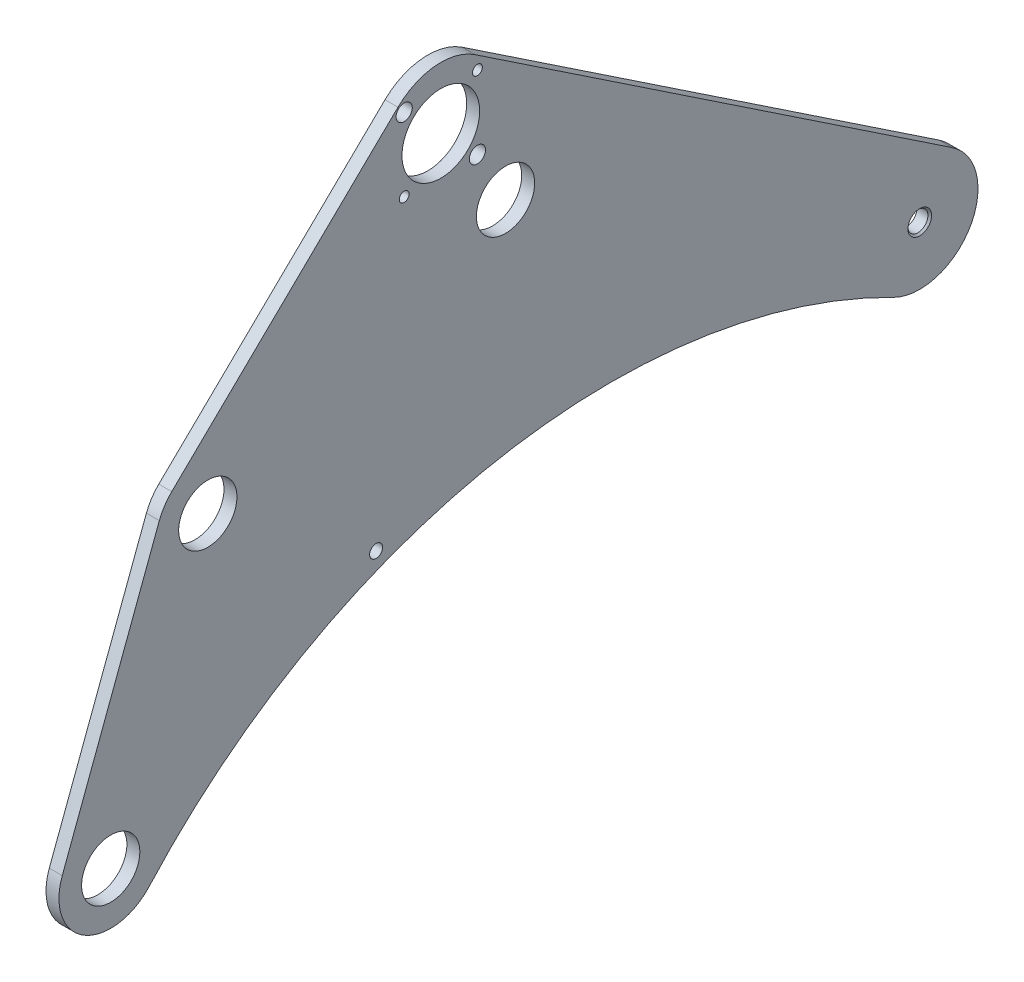
SolidWorks part; units mm, degrees
material "Acrylic (Medium-high impact)"
ref_plane "Front Plane" through (0, 0, 0) normal (0, 0, 1) x (1, 0, 0)
ref_plane "Top Plane" through (0, 0, 0) normal (0, 1, 0) x (1, 0, 0)
ref_plane "Right Plane" through (0, 0, 0) normal (1, 0, 0) x (0, 0, -1)
sketch "Sketch1" plane through (0, 0, 0) normal (1, 0, 0) x (0, 0, -1)
  line L0 (-548.7618, -304.8) -> (152.435, -304.8)
  line L1 (-192.8252, -101.6) -> (-152.4, -101.6)
  line L2 (-234.95, -143.7248) -> (-234.95, -186.4752)
  line L3 (-192.8252, -228.6) -> (-152.4, -228.6)
  line L4 (-152.4, -101.6) -> (-152.4, -228.6)
  circle A1 centre (0, 0) radius 6.35
  circle A6 centre (-396.875, -76.2) radius 9.525
  circle A7 centre (-349.25, 50.8) radius 9.525
  circle A8 centre (-203.2, 111.125) radius 9.525
  arc A9 (-234.95, -186.4752) -> (-192.8252, -228.6) centre (-192.8252, -186.4752) ccw
  arc A10 (-192.8252, -101.6) -> (-234.95, -143.7248) centre (-192.8252, -143.7248) ccw
  circle A11 centre (-355.7611, -180.5063) radius 120.65
  circle A12 centre (-234.95, 155.194) radius 29.845
  point P18 (-355.7611, -180.5063)
  dimension "D1" = 12.7
  dimension "D2" = 19.05
  dimension "D3" = 42.1248
  dimension "D4" = 127
  dimension "D7" = 203.2
  dimension "D6" = 241.3
  dimension "D16" = 59.69
  dimension "D5" = 82.55
  dimension "D8" = 304.8
  dimension "D9" = 152.4
  dimension "D10" = 396.875
  dimension "D11" = 76.2
  dimension "D12" = 349.25
  dimension "D13" = 50.8
  dimension "D14" = 203.2
  dimension "D15" = 111.125
  dimension "D17" = 234.95
  dimension "D18" = 155.194
sketch "Sketch2" plane through (0, 0, 0) normal (1, 0, 0) x (0, 0, -1)
  line L1 (-420.6578, -67.2815) -> (-373.0328, 59.7185)
  line L3 (-366.9483, 69.0189) -> (-255.9667, 176.829)
  line L5 (-218.1841, 180.2675) -> (15.8835, 23.7539)
  line L6 (-1001.8623, -101.6) -> (216.545, -101.6) construction
  line L7 (-1029.8132, 185.3565) -> (188.5941, 185.3565) construction
  arc A0 (-366.9483, 69.0189) -> (-373.0328, 59.7185) centre (-349.25, 50.8) ccw
  arc A2 (-420.6578, -67.2815) -> (-377.9906, -93.1865) centre (-396.875, -76.2) ccw
  arc A4 (-218.1841, 180.2675) -> (-255.9667, 176.829) centre (-234.95, 155.194) ccw
  arc A5 (-12.9753, -25.4592) -> (15.8835, 23.7539) centre (0, 0) ccw
  arc A8 (-377.9906, -93.1865) -> (-12.9753, -25.4592) centre (-151.3783, -297.0244) cw
  circle A12 centre (-396.875, -76.2) radius 9.525 construction
  circle A13 centre (-349.25, 50.8) radius 9.525 construction
  dimension "D1" = 25.4
  dimension "D2" = 57.15
  dimension "D3" = 60.325
  dimension "D4" = 304.8
  dimension "D6" = 286.9565
extrude "Boss-Extrude1" add sketch "Sketch2" along normal blind 6.35
sketch "Sketch3" plane through (6.35, 0, 0) normal (1, 0, 0) x (0, 0, -1)
  line L0 (-216.9895, 173.1545) -> (-252.9105, 137.2335) construction
  line L1 (-234.95, 155.194) -> (-234.95, 205.0182) construction
  line L2 (-252.9105, 173.1545) -> (-216.9895, 137.2335) construction
  circle A0 centre (-203.2, 111.125) radius 14.2875
  circle A1 centre (-349.25, 50.8) radius 14.2875
  circle A2 centre (-396.875, -76.2) radius 14.2875
  circle A3 centre (-234.95, 155.194) radius 19.05
  circle A5 centre (-252.9105, 137.2335) radius 2.413
  circle A7 centre (-216.9895, 137.2335) radius 3.9687
  circle A8 centre (-216.9895, 173.1545) radius 2.413
  circle A9 centre (-252.9105, 173.1545) radius 3.9687
  point P18 (-234.95, 155.194)
  point P28 (-234.95, 155.194)
  dimension "D1" = 38.1
  dimension "D2" = 28.575
  dimension "D3" = 4.826
  dimension "D4" = 50.8
  dimension "D5" = 45
  dimension "D6" = 7.9375
  dimension "D7" = 50.8
extrude "Cut-Extrude1" cut sketch "Sketch3" against normal up to next
hole_wizard "3/8 Clearance Hole2" positions "Sketch7" profile "Sketch8" hole size "3/8" standard "ANSI Inch" end condition through all
sketch "Sketch7" plane through (6.35, 0, 0) normal (1, 0, 0) x (0, 0, -1)
  point P0 (0, 0)
sketch "Sketch8" plane through (6.35, 0, 0) normal (0, 1, 0) x (0, 0, -1)
  line L0 (0, 0) -> (0, 6.35)
  line L1 (0, 6.35) -> (4.9022, 6.35)
  line L2 (4.9022, 6.35) -> (4.9022, 0.8915)
  line L3 (4.9022, 0.8915) -> (5.7937, 0)
  line L5 (5.7937, 0) -> (0, 0)
  line L6 (-4.9022, 0.8915) -> (-5.7937, 0) construction
  line L11 (0, -6.35) -> (0, 107.95) construction
  dimension "Thru Hole Dia." = 9.8044
  dimension "Thru Hole Depth" = 6.35
  dimension "Near C'Sink Dia." = 11.5875
  dimension "Near C'Sink Angle" = 90
sketch "Sketch9" plane through (6.35, 0, 0) normal (1, 0, 0) x (0, 0, -1)
  line L0 (-495.9857, -101.6) -> (27.4607, -101.6) construction
  line L1 (100.4878, 185.3565) -> (-422.9585, 185.3565) construction
  arc A0 (-218.1841, 180.2675) -> (-255.9667, 176.829) centre (-234.95, 155.194) ccw construction
  arc A1 (-420.6578, -67.2815) -> (-377.9906, -93.1865) centre (-396.875, -76.2) ccw construction
  dimension "D1" = 286.9565
hole_wizard "1/4 (0.2500) Dowel Hole2" positions "Sketch12" profile "Sketch13" hole size "1/4" standard "ANSI Inch" end condition through all
sketch "Sketch12" plane through (6.35, 0, 0) normal (1, 0, 0) x (0, 0, -1)
  point P0 (-266.7, -6.35)
  dimension "D1" = 266.7
sketch "Sketch13" plane through (6.35, -6.35, 266.7) normal (0, 1, 0) x (0, 0, -1)
  line L0 (0, 0) -> (0, 6.35)
  line L1 (0, 6.35) -> (3.175, 6.35)
  line L2 (3.175, 6.35) -> (3.175, 0)
  line L5 (3.175, 0) -> (0, 0)
  line L11 (0, -6.35) -> (0, 107.95) construction
  dimension "Thru Hole Dia." = 6.35
  dimension "Thru Hole Depth" = 6.35
